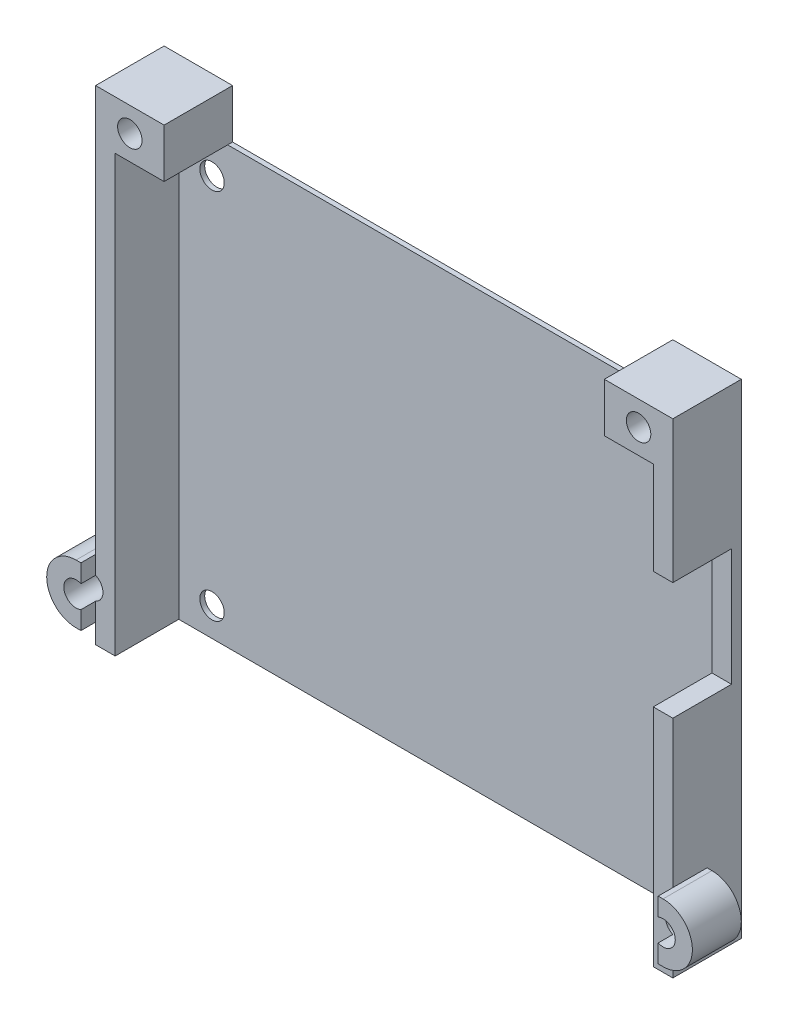
SolidWorks part; units mm, degrees
ref_plane "Front Plane" through (0, 0, 0) normal (0, 0, 1) x (1, 0, 0)
ref_plane "Top Plane" through (0, 0, 0) normal (0, 1, 0) x (1, 0, 0)
ref_plane "Right Plane" through (0, 0, 0) normal (1, 0, 0) x (0, 0, -1)
sketch "Sketch1" plane through (0, 0, 0) normal (0, 1, 0) x (1, 0, 0)
  line L0 (0, 0) -> (2, 0)
  line L1 (0, 0) -> (59, 0) construction
  line L2 (0, 0) -> (0, 7)
  line L3 (0, 7) -> (59, 7)
  line L4 (59, 0) -> (59, 7)
  line L5 (2, 0) -> (2, 6.5)
  line L6 (2, 6.5) -> (57, 6.5)
  line L7 (57, 6.5) -> (57, 0)
  line L8 (57, 0) -> (59, 0)
  dimension "D1" = 59
  dimension "D2" = 7
  dimension "D3" = 2
  dimension "D4" = 6.5
  dimension "D5" = 55
extrude "Boss-Extrude1" add sketch "Sketch1" along normal blind 44.5
sketch "Sketch2" plane through (59, 0, 0) normal (1, 0, 0) x (0, 0, -1)
  line L0 (0, 0) -> (0, 23) construction
  line L1 (0, 44.5) -> (0, 0) construction
  line L2 (0, 23) -> (6, 23)
  line L3 (6, 23) -> (6, 35)
  line L4 (6, 35) -> (0, 35)
  line L5 (0, 35) -> (0, 23)
  dimension "D1" = 23
  dimension "D2" = 6
  dimension "D3" = 12
extrude "Cut-Extrude1" cut sketch "Sketch2" against normal blind 10
sketch "Sketch3" plane through (0, 0, -7) normal (0, 0, -1) x (-1, 0, 0)
  line L0 (-59, 0) -> (-59, 8) construction
  line L1 (-59, 44.5) -> (-59, 0) construction
  line L2 (-59, 8) -> (-59, 2)
  line L3 (-59, 5) -> (-59.5, 5) construction
  line L4 (-59, 8) -> (-59.5, 8)
  line L5 (-59, 2) -> (-59.5, 2)
  line L6 (0, 0) -> (0, 8) construction
  line L7 (0, 44.5) -> (0, 0) construction
  line L8 (0, 8) -> (0.5, 8)
  line L9 (0, 8) -> (0, 2)
  line L10 (0, 2) -> (0.5, 2)
  line L11 (0, 5) -> (0.5, 5) construction
  arc A0 (-59.5, 8) -> (-59.5, 2) centre (-59.5, 5) ccw
  circle A1 centre (-59.5, 5) radius 1.25
  arc A2 (0.5, 8) -> (0.5, 2) centre (0.5, 5) cw
  circle A3 centre (0.5, 5) radius 1.25
  line M5 (0, 0) -> (0, 44.5)
  line M7 (-59, 44.5) -> (-59, 0)
  dimension "D4" = 3
  dimension "D5" = 2.5
  dimension "D11" = 3
  dimension "D12" = 2.5
  dimension "D1" = 8
  dimension "D2" = 6
  dimension "D3" = 0.5
  dimension "D6" = 8
  dimension "D7" = 0.5
  dimension "D8" = 6
  dimension "D9" = 0.5
extrude "Boss-Extrude2" add sketch "Sketch3" against normal blind 8.5 contours A1 L4 A0 L5 M7 | A3 L10 A2 L8 M5 region at (59.0695, 7.0728, -7) region at (-0.25, 7.9305, -7)
extrude "Cut-Extrude2" cut sketch "Sketch3<3>" against normal blind 11 contours L2 A1 | L9 A3 region at (58.6906, 5, -7) region at (0.3094, 5, -7)
sketch "Sketch3<3>" plane through (0, 0, -7) normal (0, 0, -1) x (-1, 0, 0) same geometry as "Sketch3"
sketch "Sketch4" plane through (0, 44.5, 0) normal (0, 1, 0) x (1, 0, 0)
  line L0 (59, 7) -> (0, 7) construction
  line L1 (0, 0) -> (7, 0)
  line L2 (0, 0) -> (0, 7)
  line L3 (0, 7) -> (7, 7)
  line L4 (7, 0) -> (7, 7)
  line L6 (59, 0) -> (52, 0)
  line L7 (59, 0) -> (59, 7)
  line L8 (59, 7) -> (52, 7)
  line L9 (52, 0) -> (52, 7)
  dimension "D1" = 7
  dimension "D2" = 7
extrude "Boss-Extrude3" add sketch "Sketch4" along normal blind 5
sketch "Sketch5" plane through (0, 0, -7) normal (0, 0, -1) x (-1, 0, 0)
  line L0 (-59, 49.5) -> (-52, 44.5) construction
  line L1 (0, 49.5) -> (-7, 44.5) construction
  circle A0 centre (-55.5, 47) radius 1.25
  circle A1 centre (-3.5, 47) radius 1.25
  dimension "D1" = 2.5
  dimension "D2" = 2.5
extrude "Cut-Extrude3" cut sketch "Sketch5" against normal through all
sketch "Sketch7" plane through (0, 0, -7) normal (0, 0, -1) x (-1, 0, 0)
  line L0 (-59, 0) -> (-59, 2.9) construction
  line L1 (-59, 2) -> (-59, 0) construction
  line L2 (-59, 2.9) -> (0, 2.9) construction
  line L3 (0, 2) -> (0, 0) construction
  line L4 (-53.6, 2.9) -> (-5.4, 2.9)
  line L5 (-53.6, 2.9) -> (-53.6, 40.95) construction
  line L6 (-53.6, 40.95) -> (-5.4, 40.95) construction
  circle A0 centre (-53.6, 2.9) radius 1.25
  circle A1 centre (-5.4, 2.9) radius 1.25
  circle A2 centre (-53.6, 40.95) radius 1.25
  circle A3 centre (-5.4, 40.95) radius 1.25
  point P11 (-29.5, 2.9)
  dimension "D3" = 2.5
  dimension "D4" = 2.5
  dimension "D6" = 2.5
  dimension "D8" = 2.5
  dimension "D1" = 2.9
  dimension "D2" = 48.2
  dimension "D5" = 38.05
  dimension "D7" = 48.2
extrude "Cut-Extrude4" cut sketch "Sketch7" against normal blind 10 contours A2 | A3 | A1 | A0 region at (5.4, 4.1146, -7) region at (54.8146, 2.9, -7) region at (53.6, 40.95, -7) region at (5.4, 40.95, -7)
extrude "Cut-Extrude6" cut sketch "Sketch3<4>" against normal blind 3.5 contours A1 L4 A0 L5 M7 | A3 L10 A2 L8 M5 region at (59.0695, 7.0728, -7) region at (-0.25, 7.9305, -7)
sketch "Sketch3<4>" plane through (0, 0, -7) normal (0, 0, -1) x (-1, 0, 0) same geometry as "Sketch3"
extrude "Boss-Extrude4" add sketch "Sketch3<5>" against normal blind 3 contours L9 A3 | L2 A1 region at (58.6906, 5, -7) region at (0.3094, 5, -7)
sketch "Sketch3<5>" plane through (0, 0, -7) normal (0, 0, -1) x (-1, 0, 0) same geometry as "Sketch3"
